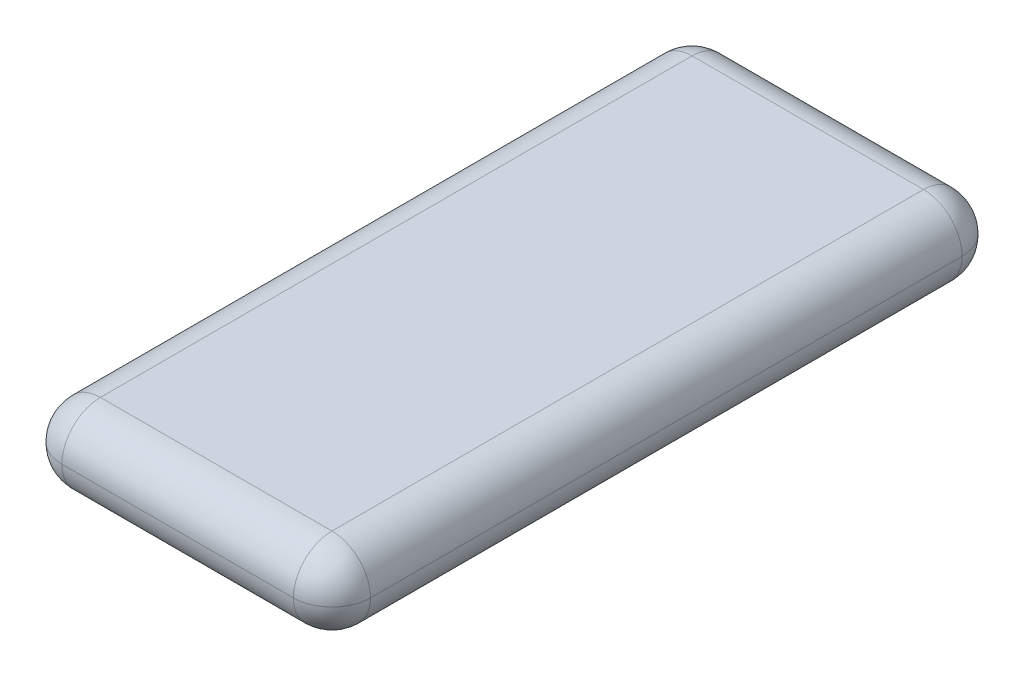
SolidWorks part; units mm, degrees
ref_plane "Front Plane" through (0, 0, 0) normal (0, 0, 1) x (1, 0, 0)
ref_plane "Top Plane" through (0, 0, 0) normal (0, 1, 0) x (1, 0, 0)
ref_plane "Right Plane" through (0, 0, 0) normal (1, 0, 0) x (0, 0, -1)
sketch "Sketch1" plane through (0, 0, 0) normal (0, 1, 0) x (1, 0, 0)
  line L1 (-6, -13) -> (6, -13)
  line L2 (-6, -13) -> (-6, 13)
  line L3 (-6, 13) -> (6, 13)
  line L4 (6, -13) -> (6, 13)
  line L5 (-6, -13) -> (6, 13) construction
  line L6 (-6, 13) -> (6, -13) construction
  point P0 (0, 0)
  dimension "D1" = 12
  dimension "D2" = 26
extrude "Boss-Extrude1" add sketch "Sketch1" along normal blind 3
fillet "Fillet1" radius 1.5 12 edges at (0, 0, -13) (6, 1.5, -13) (6, 1.5, 13) (-6, 1.5, 13) (-6, 3, 0) (-6, 1.5, -13) (0, 3, -13) (-6, 0, 0) (6, 0, 0) (6, 3, 0) (0, 0, 13) (0, 3, 13)
